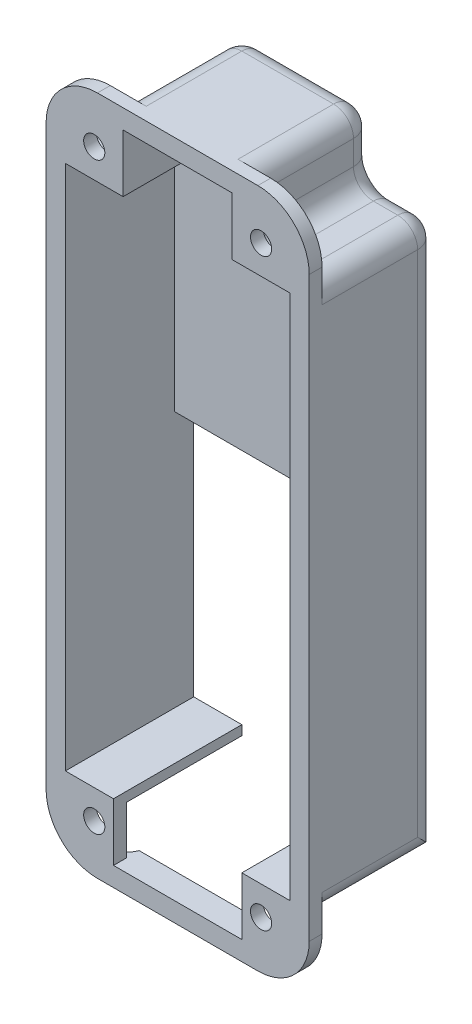
SolidWorks part; units mm, degrees
ref_plane "前视基准面" through (0, 0, 0) normal (0, 0, 1) x (1, 0, 0)
ref_plane "上视基准面" through (0, 0, 0) normal (0, 1, 0) x (1, 0, 0)
ref_plane "右视基准面" through (0, 0, 0) normal (1, 0, 0) x (0, 0, -1)
sketch "草图2" plane through (0, 0, 0) normal (0, 0, 1) x (1, 0, 0)
  line L1 (0, 0) -> (35, 0)
  line L2 (0, 0) -> (0, 100)
  line L3 (0, 100) -> (35, 100)
  line L4 (35, 0) -> (35, 100)
  line L5 (-3, -3) -> (38, -3)
  line L6 (-3, -3) -> (-3, 103)
  line L7 (-3, 103) -> (38, 103)
  line L8 (38, -3) -> (38, 103)
  line L9 (0, 100) -> (9, 100)
  line L10 (0, 100) -> (0, 91)
  line L11 (0, 91) -> (9, 91)
  line L12 (9, 100) -> (9, 91)
  line L13 (0, 100) -> (7.5, 100)
  line L14 (0, 100) -> (0, 92.5)
  line L15 (0, 92.5) -> (7.5, 92.5)
  line L16 (7.5, 100) -> (7.5, 92.5)
  line L17 (35, 100) -> (26, 100)
  line L18 (35, 100) -> (35, 91)
  line L19 (35, 91) -> (26, 91)
  line L20 (26, 100) -> (26, 91)
  line L21 (35, 100) -> (27.5, 100)
  line L22 (35, 100) -> (35, 92.5)
  line L23 (35, 92.5) -> (27.5, 92.5)
  line L24 (27.5, 100) -> (27.5, 92.5)
  line L25 (0, 0) -> (9, 0)
  line L26 (0, 0) -> (0, 9)
  line L27 (0, 9) -> (9, 9)
  line L28 (9, 0) -> (9, 9)
  line L29 (0, 0) -> (7.5, 0)
  line L30 (0, 0) -> (0, 7.5)
  line L31 (0, 7.5) -> (7.5, 7.5)
  line L32 (7.5, 0) -> (7.5, 7.5)
  line L33 (35, 0) -> (26, 0)
  line L34 (35, 0) -> (35, 9)
  line L35 (35, 9) -> (26, 9)
  line L36 (26, 0) -> (26, 9)
  line L37 (35, 0) -> (27.5, 0)
  line L38 (35, 0) -> (35, 7.5)
  line L39 (35, 7.5) -> (27.5, 7.5)
  line L40 (27.5, 0) -> (27.5, 7.5)
  circle A0 centre (4.5, 95.5) radius 1.65
  circle A1 centre (30.5, 95.5) radius 1.65
  circle A2 centre (4.5, 4.5) radius 1.65
  circle A3 centre (30.5, 4.5) radius 1.65
  dimension "D10" = 4.5
  dimension "D18" = 4.5
  dimension "D24" = 4.5
  dimension "D30" = 3
  dimension "D1" = 35
  dimension "D2" = 100
  dimension "D3" = 106
  dimension "D4" = 41
  dimension "D5" = 3
  dimension "D6" = 3
  dimension "D7" = 9
  dimension "D8" = 35
  dimension "D9" = 9
  dimension "D11" = 4.5
  dimension "D12" = 7.5
  dimension "D13" = 7.5
  dimension "D14" = 9
  dimension "D15" = 9
  dimension "D16" = 7.5
  dimension "D17" = 7.5
  dimension "D19" = 4.5
  dimension "D20" = 9
  dimension "D21" = 9
  dimension "D22" = 7.5
  dimension "D23" = 7.5
  dimension "D25" = 4.5
  dimension "D26" = 9
  dimension "D27" = 9
  dimension "D28" = 7.5
  dimension "D29" = 7.5
  dimension "D31" = 4.5
  dimension "D32" = 4.5
extrude "凸台-拉伸3" add sketch "草图2" along normal blind 17 contours L5 L8 L7 L6 L4 L33 L1 L25 L2 L26 L10 L3 L9 L17 L18 L34 | L32 L25 L28 L27 L26 L31 | L24 L3 L20 L19 L4 L23 | A0 | A2 | A3 | L38 L39 L40 L37 | A1
sketch "草图5" plane through (0, 0, 17) normal (0, 0, 1) x (1, 0, 0)
  line L2 (26, 9) -> (35, 9)
  line L3 (26, 9) -> (26, 0)
  line L4 (26, 0) -> (35, 0)
  line L5 (35, 9) -> (35, 0)
  circle A0 centre (30.5, 4.5) radius 1.65
  dimension "D3" = 4.5
  dimension "D1" = 9
  dimension "D2" = 9
  dimension "D4" = 4.5
extrude "切除-拉伸2" cut sketch "草图5" against normal through all contours A0
sketch "草图6" plane through (0, 0, 0) normal (0, 0, -1) x (-1, 0, 0)
  line L1 (-38, 103) -> (3, 103)
  line L2 (-38, 103) -> (-38, -3)
  line L3 (-38, -3) -> (3, -3)
  line L4 (3, 103) -> (3, -3)
extrude "凸台-拉伸4" add sketch "草图6" along normal blind 3
sketch "草图7" plane through (0, 0, 17) normal (0, 0, 1) x (1, 0, 0)
  line L1 (-3, 103) -> (7.5, 103)
  line L2 (-3, 103) -> (-3, 92.5)
  line L3 (-3, 92.5) -> (7.5, 92.5)
  line L4 (7.5, 103) -> (7.5, 92.5)
  line L5 (38, 103) -> (28, 103)
  line L6 (38, 103) -> (38, 93)
  line L7 (38, 93) -> (28, 93)
  line L8 (28, 103) -> (28, 93)
  line L9 (-3, -3) -> (7.5, -3)
  line L10 (-3, -3) -> (-3, 7.5)
  line L11 (-3, 7.5) -> (7.5, 7.5)
  line L12 (7.5, -3) -> (7.5, 7.5)
  line L13 (38, -3) -> (27.5, -3)
  line L14 (38, -3) -> (38, 7.5)
  line L15 (38, 7.5) -> (27.5, 7.5)
  line L16 (27.5, -3) -> (27.5, 7.5)
  dimension "D1" = 10.5
  dimension "D2" = 10.5
  dimension "D3" = 10
  dimension "D4" = 10
  dimension "D5" = 10.5
  dimension "D6" = 10.5
  dimension "D7" = 10.5
  dimension "D8" = 10.5
extrude "切除-拉伸3" cut sketch "草图7" against normal through all from offset 2 contours L10 L9 L12 L11 | L14 L13 L16 L15 | L2 L1 L4 L3 | L6 L5 L8 L7 offset against normal yes
sketch "草图9" plane through (0, 0, 17) normal (0, 0, 1) x (1, 0, 0)
  line L0 (-3, -3) -> (38, -3) construction
  line L1 (9, 9) -> (7.5, 9)
  line L2 (9, 9) -> (9, -3)
  line L3 (9, -3) -> (7.5, -3)
  line L4 (7.5, 9) -> (7.5, -3)
  line L6 (26, 9) -> (27.5, 9)
  line L7 (26, 9) -> (26, -3)
  line L8 (26, -3) -> (27.5, -3)
  line L9 (27.5, 9) -> (27.5, -3)
  line L10 (7.5, 9) -> (9, 9)
  line L11 (7.5, 9) -> (7.5, 0)
  line L12 (7.5, 0) -> (9, 0)
  line L13 (9, 9) -> (9, 0)
  line L14 (26, 9) -> (27.5, 9)
  line L15 (26, 9) -> (26, 0)
  line L16 (26, 0) -> (27.5, 0)
  line L17 (27.5, 9) -> (27.5, 0)
  circle A0 centre (4.5, 4.5) radius 1.65 construction
  circle A1 centre (30.5, 4.5) radius 1.65 construction
  line M7 (9, 9) -> (0, 9)
  line M15 (35, 9) -> (26, 9)
  line M16 (26, 9) -> (26, 0)
  line M18 (9, 0) -> (9, 9)
  dimension "D1" = 3
  dimension "D2" = 3
extrude "切除-拉伸4" cut sketch "草图9" against normal through all contours L4 L12 M18 M7 | L16 L9 M16 M15
sketch "草图10" plane through (0, 0, 0) normal (0, 0, 1) x (1, 0, 0)
  line L8 (35, 9) -> (35, 91) construction
  line L12 (9, 100) -> (26, 100) construction
  circle A0 centre (28.5, 83.63) radius 3.5
  dimension "D4" = 16.37
  dimension "D5" = 6.5
extrude "切除-拉伸7" cut sketch "草图10" against normal through all
sketch "草图12" plane through (0, 0, -3) normal (0, 0, -1) x (-1, 0, 0)
  line L1 (-27.5, 0) -> (-7.5, 0)
  line L2 (-27.5, 0) -> (-27.5, -3)
  line L3 (-27.5, -3) -> (-7.5, -3)
  line L4 (-7.5, 0) -> (-7.5, -3)
extrude "切除-拉伸8" cut sketch "草图12" against normal blind 16
sketch "草图13" plane through (0, 0, 0) normal (0, 0, 1) x (1, 0, 0)
  line L0 (0, 49) -> (0, 9)
  line L1 (0, 9) -> (0, 91) construction
  line L2 (0, 9) -> (9, 9)
  line L3 (9, 9) -> (9, 0)
  line L4 (9, 0) -> (26, 0)
  line L5 (26, 0) -> (26, 9)
  line L6 (26, 9) -> (35, 9)
  line L7 (35, 9) -> (35, 61)
  line L8 (35, 9) -> (35, 91) construction
  line L9 (35, 61) -> (26, 61)
  line L10 (26, 61) -> (26, 49)
  line L11 (26, 49) -> (0, 49)
  dimension "D1" = 9
  dimension "D2" = 52
  dimension "D3" = 26
  dimension "D4" = 40
extrude "切除-拉伸9" cut sketch "草图13" against normal through all contours L11 L0 L2 L3 L4 L5 L6 L7 L9 L10
fillet "圆角1" radius 3.1 2 edges at (-3, 50, -3) (38, 50.25, -3)
fillet "圆角2" radius 3.1 4 edges at (7.5, -1.5, 15) (27.5, -1.5, 15) (28, 93, 6) (7.5, 92.5, 6)
fillet "圆角3" radius 3.1 15 edges at (7.5, 99.3, -3) (6.592, 93.408, -3) (2.25, 92.5, -3) (-2.092, 92.5, -2.092) (28, 99.55, -3) (28.908, 93.908, -3) (33, 93, -3) (37.092, 93, -2.092) (28, 103, 6) (7.5, 103, 6) (17.75, 103, -3) (-3, 92.5, 7.55) (38, 93, 7.55) (-3, 7.5, 7.55) (38, 7.5, 7.55)
fillet "圆角4" radius 8 4 edges at (-3, 103, 16) (38, 103, 16) (38, -3, 16) (-3, -3, 16)
